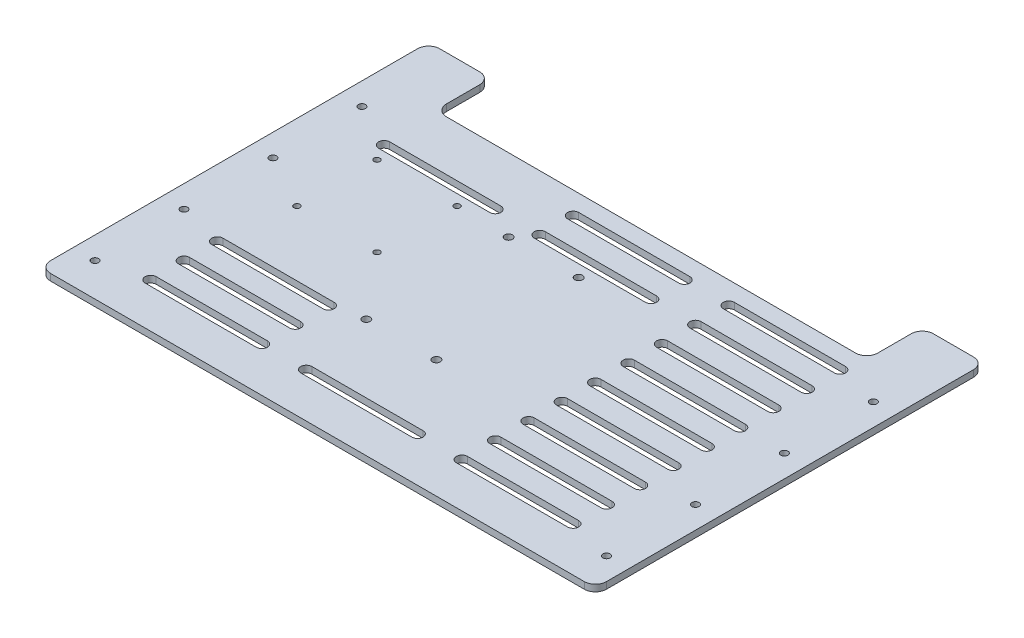
SolidWorks part; units mm, degrees
material "A-玻璃纤维"
ref_plane "前视基准面" through (0, 0, 0) normal (0, 0, 1) x (1, 0, 0)
ref_plane "上视基准面" through (0, 0, 0) normal (0, 1, 0) x (1, 0, 0)
ref_plane "右视基准面" through (0, 0, 0) normal (1, 0, 0) x (0, 0, -1)
other "Configuration Table"
sketch "草图1" plane through (0, 0, 0) normal (0, 1, 0) x (1, 0, 0)
  line L1 (-84.7342, 82.3595) -> (109.2658, 82.3595)
  line L2 (-112.7342, 55.552) -> (-112.7342, -67.6405)
  line L3 (-112.7342, -67.6405) -> (137.2658, -67.6405)
  line L4 (137.2658, 82.3595) -> (137.2658, -67.6405)
  line L5 (-112.7342, 55.552) -> (137.2658, -67.6405) construction
  line L6 (-112.7342, -67.6405) -> (137.2658, 82.3595) construction
  line L8 (-112.7342, 55.552) -> (-112.7342, 107.3595)
  line L9 (-112.7342, 107.3595) -> (-84.7342, 107.3595)
  line L10 (-84.7342, 82.3595) -> (-84.7342, 107.3595)
  line L12 (137.2658, 82.3595) -> (137.2658, 107.3595)
  line L13 (137.2658, 107.3595) -> (109.2658, 107.3595)
  line L14 (109.2658, 82.3595) -> (109.2658, 107.3595)
  point P0 (0, 0)
  dimension "D1" = 150
  dimension "D2" = 250
  dimension "D3" = 28
  dimension "D4" = 28
  dimension "D5" = 25
extrude "凸台-拉伸1" add sketch "草图1" along normal blind 3
fillet "圆角1" radius 5 8 edges at (137.2658, 1.5, 67.6405) (-112.7342, 1.5, 67.6405) (137.2658, 1.5, -107.3595) (109.2658, 1.5, -107.3595) (109.2658, 1.5, -82.3595) (-112.7342, 1.5, -107.3595) (-84.7342, 1.5, -107.3595) (-84.7342, 1.5, -82.3595)
sketch "草图4" plane through (0, 3, 0) normal (0, 1, 0) x (1, 0, 0)
  line L0 (57.2658, 72.3595) -> (107.2658, 72.3595) construction
  line L1 (57.2658, 74.8595) -> (107.2658, 74.8595)
  line L2 (57.2658, 69.8595) -> (107.2658, 69.8595)
  line L3 (57.2658, 57.3595) -> (107.2658, 57.3595) construction
  line L4 (104.2658, 82.3595) -> (-79.7342, 82.3595)
  line L5 (-112.7342, 102.3595) -> (-112.7342, -62.6405)
  line L6 (-107.7342, -67.6405) -> (132.2658, -67.6405)
  line L7 (137.2658, -62.6405) -> (137.2658, 102.3595)
  line L8 (104.2658, 82.3595) -> (-79.7342, 82.3595)
  line L9 (-112.7342, 102.3595) -> (-112.7342, -62.6405)
  line L11 (137.2658, -62.6405) -> (137.2658, 102.3595)
  line L12 (57.2658, 59.8595) -> (107.2658, 59.8595)
  line L13 (57.2658, 54.8595) -> (107.2658, 54.8595)
  line L14 (57.2658, 42.3595) -> (107.2658, 42.3595) construction
  line L15 (57.2658, 44.8595) -> (107.2658, 44.8595)
  line L16 (132.2658, 107.3595) -> (114.2658, 107.3595)
  line L17 (132.2658, 107.3595) -> (114.2658, 107.3595)
  line L18 (109.2658, 102.3595) -> (109.2658, 87.3595)
  line L19 (109.2658, 102.3595) -> (109.2658, 87.3595)
  line L20 (-84.7342, 87.3595) -> (-84.7342, 102.3595)
  line L21 (-84.7342, 87.3595) -> (-84.7342, 102.3595)
  line L22 (-89.7342, 107.3595) -> (-107.7342, 107.3595)
  line L23 (-89.7342, 107.3595) -> (-107.7342, 107.3595)
  line L24 (57.2658, 39.8595) -> (107.2658, 39.8595)
  line L25 (57.2658, 27.3595) -> (107.2658, 27.3595) construction
  line L26 (57.2658, 29.8595) -> (107.2658, 29.8595)
  line L27 (57.2658, 24.8595) -> (107.2658, 24.8595)
  line L28 (57.2658, 12.3595) -> (107.2658, 12.3595) construction
  line L29 (57.2658, 14.8595) -> (107.2658, 14.8595)
  line L30 (57.2658, 9.8595) -> (107.2658, 9.8595)
  line L31 (57.2658, -2.6405) -> (107.2658, -2.6405) construction
  line L32 (57.2658, -0.1405) -> (107.2658, -0.1405)
  line L33 (57.2658, -5.1405) -> (107.2658, -5.1405)
  line L34 (57.2658, -17.6405) -> (107.2658, -17.6405) construction
  line L35 (57.2658, -15.1405) -> (107.2658, -15.1405)
  line L36 (57.2658, -20.1405) -> (107.2658, -20.1405)
  line L37 (57.2658, -32.6405) -> (107.2658, -32.6405) construction
  line L38 (57.2658, -30.1405) -> (107.2658, -30.1405)
  line L39 (57.2658, -35.1405) -> (107.2658, -35.1405)
  line L40 (57.2658, -47.6405) -> (107.2658, -47.6405) construction
  line L41 (57.2658, -45.1405) -> (107.2658, -45.1405)
  line L42 (57.2658, -50.1405) -> (107.2658, -50.1405)
  line L52 (-12.7342, 72.3595) -> (37.2658, 72.3595) construction
  line L53 (-12.7342, 74.8595) -> (37.2658, 74.8595)
  line L54 (-12.7342, 69.8595) -> (37.2658, 69.8595)
  line L55 (-12.7342, 57.3595) -> (37.2658, 57.3595) construction
  line L56 (-12.7342, 59.8595) -> (37.2658, 59.8595)
  line L57 (-12.7342, 54.8595) -> (37.2658, 54.8595)
  line L58 (-82.7342, 72.3595) -> (-32.7342, 72.3595) construction
  line L59 (-82.7342, 74.8595) -> (-32.7342, 74.8595)
  line L60 (-82.7342, 69.8595) -> (-32.7342, 69.8595)
  line L61 (-82.7342, 57.3595) -> (-32.7342, 57.3595) construction
  line L62 (-82.7342, 59.8595) -> (-32.7342, 59.8595)
  line L63 (-82.7342, 54.8595) -> (-32.7342, 54.8595)
  line L64 (-12.7342, -47.6405) -> (37.2658, -47.6405) construction
  line L65 (-12.7342, -45.1405) -> (37.2658, -45.1405)
  line L66 (-12.7342, -50.1405) -> (37.2658, -50.1405)
  line L76 (-82.7342, -47.6405) -> (-32.7342, -47.6405) construction
  line L77 (-82.7342, -45.1405) -> (-32.7342, -45.1405)
  line L78 (-82.7342, -50.1405) -> (-32.7342, -50.1405)
  line L88 (-82.7342, -32.6405) -> (-32.7342, -32.6405) construction
  line L89 (-82.7342, -30.1405) -> (-32.7342, -30.1405)
  line L90 (-82.7342, -35.1405) -> (-32.7342, -35.1405)
  line L91 (-82.7342, -17.6405) -> (-32.7342, -17.6405) construction
  line L92 (-82.7342, -15.1405) -> (-32.7342, -15.1405)
  line L93 (-82.7342, -20.1405) -> (-32.7342, -20.1405)
  line L149 (57.2658, -77.6405) -> (107.2658, -77.6405) construction
  line L150 (57.2658, -75.1405) -> (107.2658, -75.1405)
  line L151 (57.2658, -80.1405) -> (107.2658, -80.1405)
  line L152 (57.2658, -92.6405) -> (107.2658, -92.6405) construction
  line L153 (57.2658, -90.1405) -> (107.2658, -90.1405)
  line L154 (57.2658, -95.1405) -> (107.2658, -95.1405)
  line L155 (57.2658, -62.6405) -> (107.2658, -62.6405) construction
  line L156 (57.2658, -60.1405) -> (107.2658, -60.1405)
  line L157 (57.2658, -65.1405) -> (107.2658, -65.1405)
  line L158 (57.2658, -77.6405) -> (107.2658, -77.6405) construction
  line L159 (57.2658, -75.1405) -> (107.2658, -75.1405)
  line L160 (57.2658, -80.1405) -> (107.2658, -80.1405)
  line L161 (57.2658, -92.6405) -> (107.2658, -92.6405) construction
  line L162 (57.2658, -90.1405) -> (107.2658, -90.1405)
  line L163 (57.2658, -95.1405) -> (107.2658, -95.1405)
  line L164 (57.2658, -62.6405) -> (107.2658, -62.6405) construction
  line L165 (57.2658, -60.1405) -> (107.2658, -60.1405)
  line L166 (57.2658, -65.1405) -> (107.2658, -65.1405)
  circle A0 centre (-18.8913, -14.5) radius 1.75 construction
  circle A1 centre (12.6087, -14.5) radius 1.75 construction
  circle A2 centre (-42.5828, 49.995) radius 1.35 construction
  circle A3 centre (-18.8913, 49.5) radius 1.75 construction
  arc A4 (57.2658, 74.8595) -> (57.2658, 69.8595) centre (57.2658, 72.3595) ccw
  arc A5 (-112.7342, -62.6405) -> (-107.7342, -67.6405) centre (-107.7342, -62.6405) ccw
  arc A6 (132.2658, -67.6405) -> (137.2658, -62.6405) centre (132.2658, -62.6405) ccw
  arc A7 (107.2658, 69.8595) -> (107.2658, 74.8595) centre (107.2658, 72.3595) ccw
  arc A9 (-112.7342, -62.6405) -> (-107.7342, -67.6405) centre (-107.7342, -62.6405) ccw
  arc A10 (132.2658, -67.6405) -> (137.2658, -62.6405) centre (132.2658, -62.6405) ccw
  circle A12 centre (12.6087, 49.5) radius 1.75 construction
  circle A13 centre (-18.8913, -14.5) radius 1.75
  circle A14 centre (12.6087, -14.5) radius 1.75
  circle A15 centre (-42.5828, 49.995) radius 1.35
  circle A16 centre (-18.8913, 49.5) radius 1.75
  circle A17 centre (12.6087, 49.5) radius 1.75
  circle A18 centre (-42.5828, 13.995) radius 1.35 construction
  circle A19 centre (-78.5828, 13.995) radius 1.35 construction
  circle A20 centre (-78.5828, 49.995) radius 1.35 construction
  circle A21 centre (-42.5828, 13.995) radius 1.35
  circle A22 centre (-78.5828, 13.995) radius 1.35
  circle A23 centre (-78.5828, 49.995) radius 1.35
  arc A24 (57.2658, 59.8595) -> (57.2658, 54.8595) centre (57.2658, 57.3595) ccw
  arc A25 (107.2658, 54.8595) -> (107.2658, 59.8595) centre (107.2658, 57.3595) ccw
  arc A26 (57.2658, 44.8595) -> (57.2658, 39.8595) centre (57.2658, 42.3595) ccw
  arc A27 (107.2658, 39.8595) -> (107.2658, 44.8595) centre (107.2658, 42.3595) ccw
  arc A28 (57.2658, 29.8595) -> (57.2658, 24.8595) centre (57.2658, 27.3595) ccw
  arc A29 (107.2658, 24.8595) -> (107.2658, 29.8595) centre (107.2658, 27.3595) ccw
  arc A30 (57.2658, 14.8595) -> (57.2658, 9.8595) centre (57.2658, 12.3595) ccw
  arc A32 (107.2658, 9.8595) -> (107.2658, 14.8595) centre (107.2658, 12.3595) ccw
  arc A34 (57.2658, -0.1405) -> (57.2658, -5.1405) centre (57.2658, -2.6405) ccw
  arc A36 (107.2658, -5.1405) -> (107.2658, -0.1405) centre (107.2658, -2.6405) ccw
  arc A38 (57.2658, -15.1405) -> (57.2658, -20.1405) centre (57.2658, -17.6405) ccw
  arc A40 (107.2658, -20.1405) -> (107.2658, -15.1405) centre (107.2658, -17.6405) ccw
  arc A42 (57.2658, -30.1405) -> (57.2658, -35.1405) centre (57.2658, -32.6405) ccw
  arc A43 (107.2658, -35.1405) -> (107.2658, -30.1405) centre (107.2658, -32.6405) ccw
  arc A44 (57.2658, -45.1405) -> (57.2658, -50.1405) centre (57.2658, -47.6405) ccw
  arc A45 (107.2658, -50.1405) -> (107.2658, -45.1405) centre (107.2658, -47.6405) ccw
  arc A52 (-12.7342, 74.8595) -> (-12.7342, 69.8595) centre (-12.7342, 72.3595) ccw
  arc A53 (37.2658, 69.8595) -> (37.2658, 74.8595) centre (37.2658, 72.3595) ccw
  arc A54 (-12.7342, 59.8595) -> (-12.7342, 54.8595) centre (-12.7342, 57.3595) ccw
  arc A55 (37.2658, 54.8595) -> (37.2658, 59.8595) centre (37.2658, 57.3595) ccw
  arc A56 (-82.7342, 74.8595) -> (-82.7342, 69.8595) centre (-82.7342, 72.3595) ccw
  arc A57 (-32.7342, 69.8595) -> (-32.7342, 74.8595) centre (-32.7342, 72.3595) ccw
  arc A58 (-82.7342, 59.8595) -> (-82.7342, 54.8595) centre (-82.7342, 57.3595) ccw
  arc A59 (-32.7342, 54.8595) -> (-32.7342, 59.8595) centre (-32.7342, 57.3595) ccw
  arc A60 (-12.7342, -45.1405) -> (-12.7342, -50.1405) centre (-12.7342, -47.6405) ccw
  arc A61 (37.2658, -50.1405) -> (37.2658, -45.1405) centre (37.2658, -47.6405) ccw
  arc A68 (-82.7342, -45.1405) -> (-82.7342, -50.1405) centre (-82.7342, -47.6405) ccw
  arc A69 (-32.7342, -50.1405) -> (-32.7342, -45.1405) centre (-32.7342, -47.6405) ccw
  arc A76 (-82.7342, -30.1405) -> (-82.7342, -35.1405) centre (-82.7342, -32.6405) ccw
  arc A77 (-32.7342, -35.1405) -> (-32.7342, -30.1405) centre (-32.7342, -32.6405) ccw
  arc A78 (-82.7342, -15.1405) -> (-82.7342, -20.1405) centre (-82.7342, -17.6405) ccw
  arc A79 (-32.7342, -20.1405) -> (-32.7342, -15.1405) centre (-32.7342, -17.6405) ccw
  arc A88 (137.2658, 102.3595) -> (132.2658, 107.3595) centre (132.2658, 102.3595) ccw
  arc A89 (137.2658, 102.3595) -> (132.2658, 107.3595) centre (132.2658, 102.3595) ccw
  arc A90 (114.2658, 107.3595) -> (109.2658, 102.3595) centre (114.2658, 102.3595) ccw
  arc A91 (114.2658, 107.3595) -> (109.2658, 102.3595) centre (114.2658, 102.3595) ccw
  arc A92 (104.2658, 82.3595) -> (109.2658, 87.3595) centre (104.2658, 87.3595) ccw
  arc A93 (104.2658, 82.3595) -> (109.2658, 87.3595) centre (104.2658, 87.3595) ccw
  arc A94 (-84.7342, 87.3595) -> (-79.7342, 82.3595) centre (-79.7342, 87.3595) ccw
  arc A95 (-84.7342, 87.3595) -> (-79.7342, 82.3595) centre (-79.7342, 87.3595) ccw
  arc A96 (-84.7342, 102.3595) -> (-89.7342, 107.3595) centre (-89.7342, 102.3595) ccw
  arc A97 (-84.7342, 102.3595) -> (-89.7342, 107.3595) centre (-89.7342, 102.3595) ccw
  arc A98 (-107.7342, 107.3595) -> (-112.7342, 102.3595) centre (-107.7342, 102.3595) ccw
  arc A99 (-107.7342, 107.3595) -> (-112.7342, 102.3595) centre (-107.7342, 102.3595) ccw
  arc A140 (57.2658, -75.1405) -> (57.2658, -80.1405) centre (57.2658, -77.6405) ccw
  arc A141 (107.2658, -80.1405) -> (107.2658, -75.1405) centre (107.2658, -77.6405) ccw
  arc A142 (57.2658, -90.1405) -> (57.2658, -95.1405) centre (57.2658, -92.6405) ccw
  arc A143 (107.2658, -95.1405) -> (107.2658, -90.1405) centre (107.2658, -92.6405) ccw
  arc A144 (57.2658, -60.1405) -> (57.2658, -65.1405) centre (57.2658, -62.6405) ccw
  arc A145 (107.2658, -65.1405) -> (107.2658, -60.1405) centre (107.2658, -62.6405) ccw
  point P38 (82.2658, 72.3595)
  point P47 (82.2658, 57.3595)
  point P54 (82.2658, 42.3595)
  point P61 (82.2658, 27.3595)
  point P68 (82.2658, 12.3595)
  point P75 (82.2658, -2.6405)
  point P82 (82.2658, -17.6405)
  point P89 (82.2658, -32.6405)
  point P96 (82.2658, -47.6405)
  point P103 (82.2658, -82.6405)
  point P110 (82.2658, -97.6405)
  point P124 (12.2658, 72.3595)
  point P131 (12.2658, 57.3595)
  point P138 (-57.7342, 72.3595)
  point P145 (-57.7342, 57.3595)
  point P152 (12.2658, -47.6405)
  point P159 (12.2658, -82.6405)
  point P166 (12.2658, -97.6405)
  point P173 (82.2658, -67.6405)
  point P180 (-57.7342, -47.6405)
  point P187 (-57.7342, -82.6405)
  point P194 (-57.7342, -97.6405)
  point P201 (12.2658, -67.6405)
  point P208 (-57.7342, -32.6405)
  point P215 (-57.7342, -17.6405)
  point P220 (-57.7342, -67.6405)
  point P272 (82.2658, -82.6405)
  point P279 (82.2658, -97.6405)
  point P286 (82.2658, -67.6405)
  point P293 (82.2658, -82.6405)
  point P300 (82.2658, -97.6405)
  point P307 (82.2658, -67.6405)
  point P314 (82.2658, -82.6405)
  point P321 (82.2658, -97.6405)
  point P328 (82.2658, -67.6405)
  point P335 (82.2658, -77.6405)
  point P342 (82.2658, -92.6405)
  point P349 (82.2658, -62.6405)
  point P356 (82.2658, -77.6405)
  point P363 (82.2658, -92.6405)
  point P370 (82.2658, -62.6405)
  point P377 (82.2658, -77.6405)
  point P384 (82.2658, -92.6405)
  point P391 (82.2658, -62.6405)
  dimension "D4" = 2.5
  dimension "D2" = 30
  dimension "D3" = 50
  dimension "D5" = 10
  dimension "D1" = 0
  dimension "D6" = 12
  dimension "D7" = 3
  dimension "D8" = 3
  dimension "D9" = 3
extrude "切除-拉伸2" cut sketch "草图4" against normal blind 10 contours A17 | A13 | A15 | A22 | A21 | A14 | A16 | A23 region at (-18.8913, 3, 14.5) region at (-42.5828, 3, -49.995) region at (12.6087, 3, -49.5) region at (-42.5828, 3, -13.995) region at (-78.5828, 3, -13.995)
extrude "切除-拉伸3" cut sketch "草图4<3>" against normal blind 10 contours L63 A59 L62 A58 | L54 A53 L53 A52 | L57 A55 L56 A54 | L93 A79 L92 A78 | L90 A77 L89 A76 | L78 A69 L77 A68 | L66 A61 L65 A60 | L42 A45 L41 A44 | L39 A43 L38 A42 | L36 A40 L35 A38 | L33 A36 L32 A34 | L30 A32 L29 A30 | L27 A29 L26 A28 | L24 A27 L15 A26 | L13 A25 L12 A24 | L2 A7 L1 A4
sketch "草图4<3>" plane through (0, 3, 0) normal (0, 1, 0) x (1, 0, 0) same geometry as "草图4"
sketch "草图5" plane through (0, 3, 0) normal (0, 1, 0) x (1, 0, 0)
  line L0 (12.2658, 82.3595) -> (12.2658, -94.0338) construction
  line L1 (104.2658, 82.3595) -> (-79.7342, 82.3595) construction
  line L2 (-112.7342, 102.3595) -> (-112.7342, -62.6405) construction
  line L3 (-89.7342, 107.3595) -> (-107.7342, 107.3595) construction
  circle A0 centre (-102.7342, 67.3595) radius 1.6
  circle A1 centre (-102.7342, 27.3595) radius 1.6
  circle A2 centre (-102.7342, -12.6405) radius 1.6
  circle A3 centre (-102.7342, -52.6405) radius 1.6
  circle A4 centre (127.2658, -52.6405) radius 1.6
  circle A5 centre (127.2658, -12.6405) radius 1.6
  circle A6 centre (127.2658, 27.3595) radius 1.6
  circle A7 centre (127.2658, 67.3595) radius 1.6
  dimension "D1" = 3.2
  dimension "D2" = 10
  dimension "D3" = 40
  dimension "D5" = 40
  dimension "D4" = 4
extrude "切除-拉伸4" cut sketch "草图5" against normal blind 10
